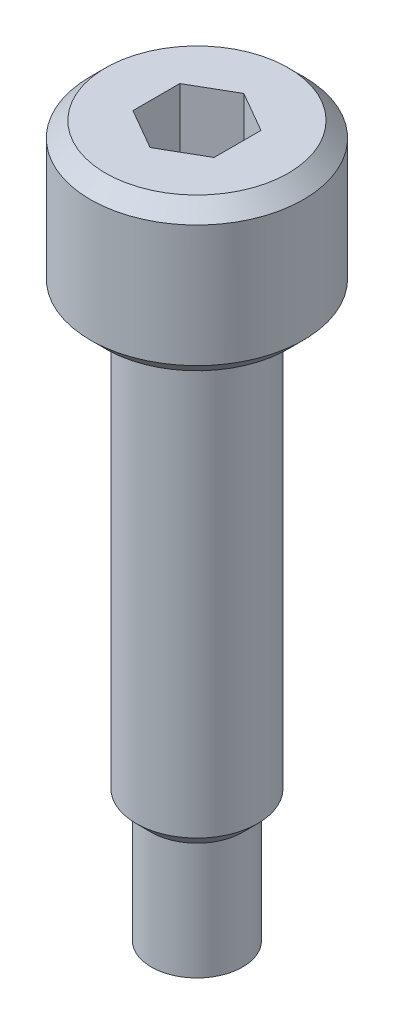
SolidWorks part; units mm, degrees
ref_plane "Front Plane" through (0, 0, 0) normal (0, 0, 1) x (1, 0, 0)
ref_plane "Top Plane" through (0, 0, 0) normal (0, 1, 0) x (1, 0, 0)
ref_plane "Right Plane" through (0, 0, 0) normal (1, 0, 0) x (0, 0, -1)
sketch "Sketch1" plane through (0, 0, 0) normal (0, 0, 1) x (1, 0, 0)
  line L0 (0, 0) -> (4.5, 0)
  line L1 (4.5, 0) -> (4.5, 11.5)
  line L2 (4.5, 11.5) -> (6, 11.5)
  line L3 (6, 11.5) -> (6, 55)
  line L4 (6, 55) -> (10.5, 55)
  line L5 (10.5, 55) -> (10.5, 70)
  line L6 (10.5, 70) -> (0, 70)
  line L7 (0, 70) -> (0, 0)
  dimension "D1" = 4.5
  dimension "D2" = 11.5
  dimension "D3" = 70
  dimension "D4" = 15
  dimension "D5" = 6
  dimension "D6" = 10.5
revolve "Revolve1" add sketch "Sketch1" angle 360 about L7
chamfer "Chamfer1" distance 1.5 angle 45 3 edges at (-6, 11.5, 0) (-10.5, 55, 0) (-10.5, 70, 0)
sketch "Sketch2" plane through (0, 70, 0) normal (0, 1, 0) x (1, 0, 0)
  line L1 (0, 4.6188) -> (-4, 2.3094)
  line L2 (-4, 2.3094) -> (-4, -2.3094)
  line L3 (-4, -2.3094) -> (0, -4.6188)
  line L4 (0, -4.6188) -> (4, -2.3094)
  line L5 (4, -2.3094) -> (4, 2.3094)
  line L6 (4, 2.3094) -> (0, 4.6188)
  circle A0 centre (0, 0) radius 4 construction
  dimension "D1" = 8
extrude "Cut-Extrude1" cut sketch "Sketch2" against normal blind 8
